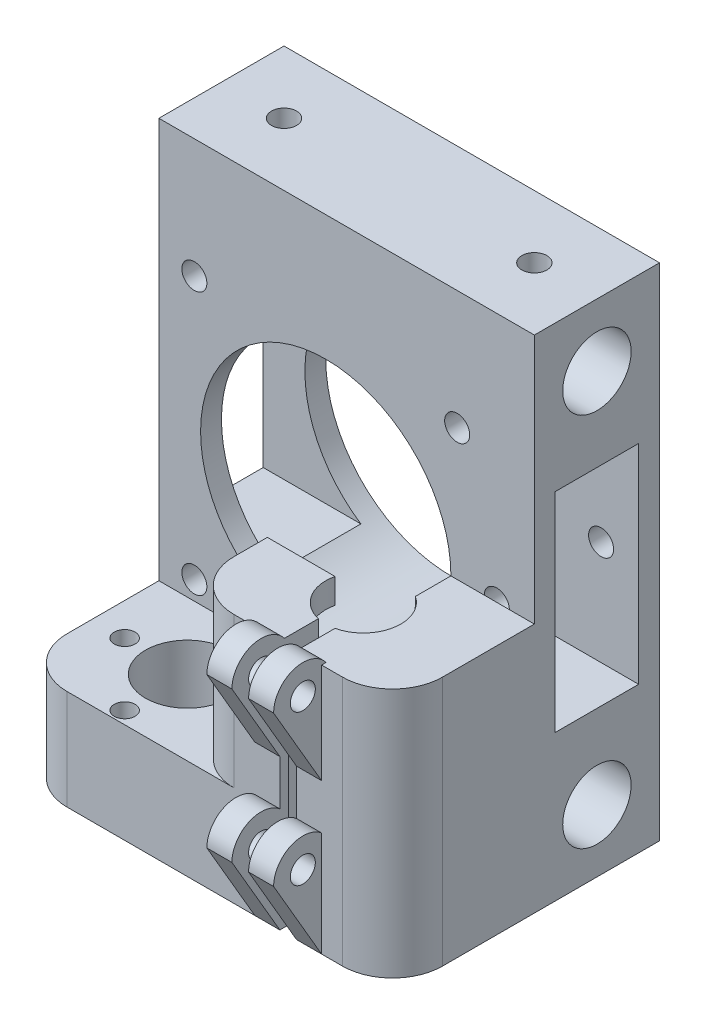
SolidWorks part; units mm, degrees
ref_plane "Front Plane" through (0, 0, 0) normal (0, 0, 1) x (1, 0, 0)
ref_plane "Top Plane" through (0, 0, 0) normal (0, 1, 0) x (1, 0, 0)
ref_plane "Right Plane" through (0, 0, 0) normal (1, 0, 0) x (0, 0, -1)
sketch "Sketch1" plane through (0, 0, 0) normal (0, 0, 1) x (1, 0, 0)
  line L1 (-22.5, -30) -> (22.5, -30)
  line L2 (-22.5, -30) -> (-22.5, 30)
  line L3 (-22.5, 30) -> (22.5, 30)
  line L4 (22.5, -30) -> (22.5, 30)
  line L5 (-22.5, -30) -> (22.5, 30) construction
  line L6 (-22.5, 30) -> (22.5, -30) construction
  point P0 (0, 0)
  dimension "D1" = 45
  dimension "D2" = 60
extrude "Boss-Extrude1" add sketch "Sketch1" along normal blind 15
sketch "Sketch2" plane through (22.5, 0, 0) normal (1, 0, 0) x (0, 0, -1)
  line L0 (-7.5, 30) -> (-7.5, -30) construction
  line L1 (-15, 30) -> (0, 30) construction
  line L2 (-15, -30) -> (0, -30) construction
  line L3 (0, -30) -> (0, 30) construction
  line L4 (-12.5, -12.5) -> (-2.5, -12.5)
  line L5 (-12.5, -12.5) -> (-12.5, 12.5)
  line L6 (-12.5, 12.5) -> (-2.5, 12.5)
  line L7 (-2.5, -12.5) -> (-2.5, 12.5)
  line L8 (-12.5, -12.5) -> (-2.5, 12.5) construction
  line L9 (-12.5, 12.5) -> (-2.5, -12.5) construction
  line L10 (-15, 0) -> (0, 0) construction
  line L11 (-15, -30) -> (-15, 30) construction
  circle A0 centre (-7.5, 22.5) radius 4.1
  circle A1 centre (-7.5, -22.5) radius 4.1
  point P6 (-7.5, 0)
  dimension "D3" = 8.2
  dimension "D1" = 2.5
  dimension "D2" = 25
  dimension "D4" = 22.5
extrude "Cut-Extrude1" cut sketch "Sketch2" against normal through all
sketch "Sketch3" plane through (-22.5, 0, 0) normal (-1, 0, 0) x (0, 0, 1)
  line L1 (15, -30) -> (32, -30)
  line L2 (15, -30) -> (15, -18)
  line L3 (15, -18) -> (32, -18)
  line L4 (32, -30) -> (32, -18)
  dimension "D1" = 17
  dimension "D2" = 12
extrude "Boss-Extrude2" add sketch "Sketch3" against normal up to surface (45 mm away) up to face at (22.5, -22.5, 11.6)
sketch "Sketch4" plane through (0, -18, 0) normal (0, 1, 0) x (1, 0, 0)
  line L0 (22.5, -15) -> (-22.5, -15) construction
  line L1 (22.5, -32) -> (-2.5, -32)
  line L2 (22.5, -32) -> (22.5, -15)
  line L3 (22.5, -15) -> (-2.5, -15)
  line L4 (-2.5, -32) -> (-2.5, -15)
  dimension "D1" = 25
extrude "Boss-Extrude3" add sketch "Sketch4" along normal blind 18
sketch "Sketch5" plane through (0, 0, 32) normal (0, 0, 1) x (1, 0, 0)
  line L0 (10, 0) -> (10, -30) construction
  line L1 (22.5, 0) -> (-2.5, 0) construction
  line L2 (22.5, -30) -> (-22.5, -30) construction
  line L3 (-2.5, 0) -> (22.5, 0) construction
  line L4 (9, -30) -> (11, -30)
  line L5 (9, -30) -> (9, 0)
  line L6 (9, 0) -> (11, 0)
  line L7 (11, -30) -> (11, 0)
  line L8 (9, -30) -> (11, 0) construction
  line L9 (9, 0) -> (11, -30) construction
  point P6 (10, -15)
  dimension "D1" = 2
extrude "Cut-Extrude2" cut sketch "Sketch5" against normal blind 5
sketch "Sketch6" plane through (0, -30, 0) normal (0, -1, 0) x (1, 0, 0)
  line L0 (10, 27) -> (10, 15) construction
  line L1 (11, 27) -> (9, 27) construction
  line L2 (22.5, 15) -> (-2.5, 15) construction
  circle A0 centre (10, 23) radius 4.5
  dimension "D1" = 9
  dimension "D2" = 4
extrude "Cut-Extrude3" cut sketch "Sketch6" against normal through all
sketch "Sketch7" plane through (0, -30, 0) normal (0, -1, 0) x (1, 0, 0)
  line L0 (10, 23) -> (-22.5, 23) construction
  line L1 (-22.5, 32) -> (-22.5, 0) construction
  line L2 (-11.1, 23) -> (-7.5645, 26.5355) construction
  line L3 (-11.1, 23) -> (-11.1, 30.5) construction
  line L4 (-11.1, 23) -> (-7.5645, 19.4645) construction
  circle A0 centre (10, 23) radius 8
  circle A1 centre (-11.1, 23) radius 5
  circle A2 centre (-3.6, 23) radius 1.25
  circle A3 centre (-11.1, 30.5) radius 1.25
  circle A4 centre (-11.1, 15.5) radius 1.25
  circle A5 centre (-18.6, 23) radius 1.25
  dimension "D1" = 16
  dimension "D2" = 10
  dimension "D4" = 2.5
  dimension "D8" = 2.5
  dimension "D3" = 21.1
  dimension "D5" = 7.5
  dimension "D6" = 45
  dimension "D7" = 7.5
  dimension "D9" = 45
extrude "Cut-Extrude4" cut sketch "Sketch7" against normal offset from surface (27 mm away) 3 up to face at (10, 0, 25.4859)
sketch "Sketch8" plane through (0, 0, 0) normal (0, 0, -1) x (-1, 0, 0)
  line L0 (2.5, -30) -> (2.5, 30) construction
  line L3 (-22.5, 0) -> (22.5, 0) construction
  line L4 (-22.5, -30) -> (-22.5, 30) construction
  line L5 (22.5, 30) -> (22.5, -30) construction
  line L6 (2.5, 0) -> (18.25, 15.75) construction
  line L7 (22.5, -30) -> (-22.5, -30) construction
  line L8 (-22.5, 30) -> (22.5, 30) construction
  line L9 (-13.25, -15.75) -> (2.5, 0) construction
  line L10 (18.25, -15.75) -> (2.5, 0) construction
  line L11 (2.5, 0) -> (-13.25, 15.75) construction
  circle A0 centre (2.5, 0) radius 15
  circle A1 centre (18.25, 15.75) radius 1.5
  circle A2 centre (-13.25, 15.75) radius 1.5
  circle A3 centre (-13.25, -15.75) radius 1.5
  circle A4 centre (18.25, -15.75) radius 1.5
  dimension "D1" = 30
  dimension "D2" = 3
  dimension "D10" = 3
  dimension "D3" = 0
  dimension "D4" = 45
  dimension "D5" = 31.5
  dimension "D6" = 31.5
  dimension "D7" = 20
  dimension "D8" = 45
  dimension "D9" = 45
extrude "Cut-Extrude5" cut sketch "Sketch8" against normal blind 22
fillet "Fillet1" radius 6 3 edges at (-22.5, -24, 32) (-2.5, -9, 32) (22.5, -15, 32)
sketch "Sketch9" plane through (0, 0, 0) normal (0, 0, -1) x (-1, 0, 0)
  line L0 (-22.5, 0) -> (-12.5, 0) construction
  line L1 (-22.5, -30) -> (-22.5, 30) construction
  circle A0 centre (2.5, 0) radius 15 construction
  circle A1 centre (-18, 0) radius 1.5
  dimension "D1" = 3
  dimension "D2" = 4.5
extrude "Cut-Extrude6" cut sketch "Sketch9" against normal up to surface (15 mm away) up to face at (-19.75, -15.75, 15)
sketch "Sketch10" plane through (0, 30, 0) normal (0, 1, 0) x (1, 0, 0)
  line L0 (-22.5, -7.5) -> (22.5, -7.5) construction
  line L1 (-22.5, -15) -> (-22.5, 0) construction
  line L2 (22.5, -15) -> (22.5, 0) construction
  line L3 (0, -15) -> (0, 0) construction
  line L4 (22.5, -15) -> (-22.5, -15) construction
  circle A0 centre (-15, -7.5) radius 1.5
  circle A1 centre (15, -7.5) radius 1.5
  dimension "D1" = 3
  dimension "D2" = 15
extrude "Cut-Extrude7" cut sketch "Sketch10" against normal blind 5
extrude "Cut-Extrude8" cut sketch "Sketch10<2>" along normal blind 5 from surface starting at face at (-18.6, -30, 24.25)
sketch "Sketch10<2>" plane through (0, 30, 0) normal (0, 1, 0) x (1, 0, 0) same geometry as "Sketch10"
sketch "Sketch12" plane through (9, 0, 0) normal (1, 0, 0) x (0, 0, -1)
  line L0 (-32, -30) -> (-37.75, -20.1131)
  line L1 (-30.9373, -18.9837) -> (-30.9373, -30)
  line L2 (-30.9373, -30) -> (-30.9373, -3) construction
  line L3 (-30.9373, -30) -> (-32, -30) construction
  line L4 (-32, -30) -> (-30.9373, -30)
  line L5 (-32, -12) -> (-37.75, -2.1131)
  line L6 (-30.9373, -0.9837) -> (-30.9373, -12)
  line L7 (-32, -12) -> (-30.9373, -12)
  circle A0 centre (-34.25, -20.1131) radius 1.5
  arc A1 (-30.9373, -18.9837) -> (-37.75, -20.1131) centre (-34.25, -20.1131) ccw
  arc A2 (-30.9373, -0.9837) -> (-37.75, -2.1131) centre (-34.25, -2.1131) ccw
  circle A3 centre (-34.25, -2.1131) radius 1.5
  point P7 (-31.4686, -30)
  dimension "D1" = 3
  dimension "D2" = 2
  dimension "D8" = 1.0627
  dimension "D9" = 3.3127
  dimension "D3" = 0
  dimension "D4" = 0
  dimension "D5" = 0
  dimension "D7" = 120.181
  dimension "D6" = 2
extrude "Boss-Extrude4" add sketch "Sketch12" against normal blind 3
extrude "Boss-Extrude5" add sketch "Sketch12<3>" along normal blind 3 from offset 2
sketch "Sketch12<3>" plane through (9, 0, 0) normal (1, 0, 0) x (0, 0, -1) same geometry as "Sketch12"
